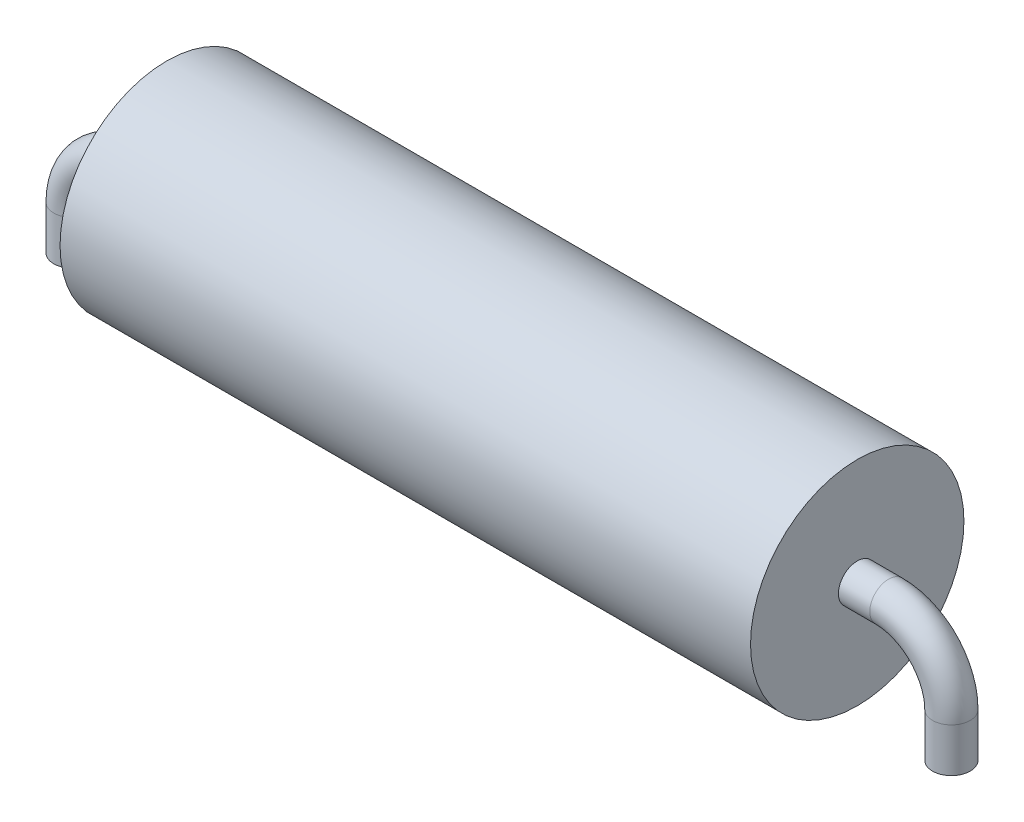
SolidWorks part; units mm, degrees
ref_plane "Спереди" through (0, 0, 0) normal (0, 0, 1) x (1, 0, 0)
ref_plane "Сверху" through (0, 0, 0) normal (0, 1, 0) x (1, 0, 0)
ref_plane "Справа" through (0, 0, 0) normal (1, 0, 0) x (0, 0, -1)
other "Configuration Table"
sketch "Sketch1" plane through (0, 0, 0) normal (1, 0, 0) x (0, 0, -1)
  circle A0 centre (0, 0) radius 1.7
extrude "Boss-Extrude1" add sketch "Sketch1" along normal blind 5.5 and the other way blind 5.5
sketch "Sketch2" plane through (0, 0, 0) normal (0, 0, 1) x (1, 0, 0)
  line L0 (-5.5, 0) -> (-6, 0)
  line L1 (-5.5, 1.7) -> (-5.5, -1.7) construction
  line L2 (-7, -1) -> (-7, -1.7)
  arc A0 (-6, 0) -> (-7, -1) centre (-6, -1) ccw
  dimension "D1" = 1
sweep "Sweep1" add path "Sketch2" circular profile diameter 0.6 parameters "D3"=0.6
mirror "Mirror1" about plane through (0, 0, 0) normal (1, 0, 0) of "Sweep1"
